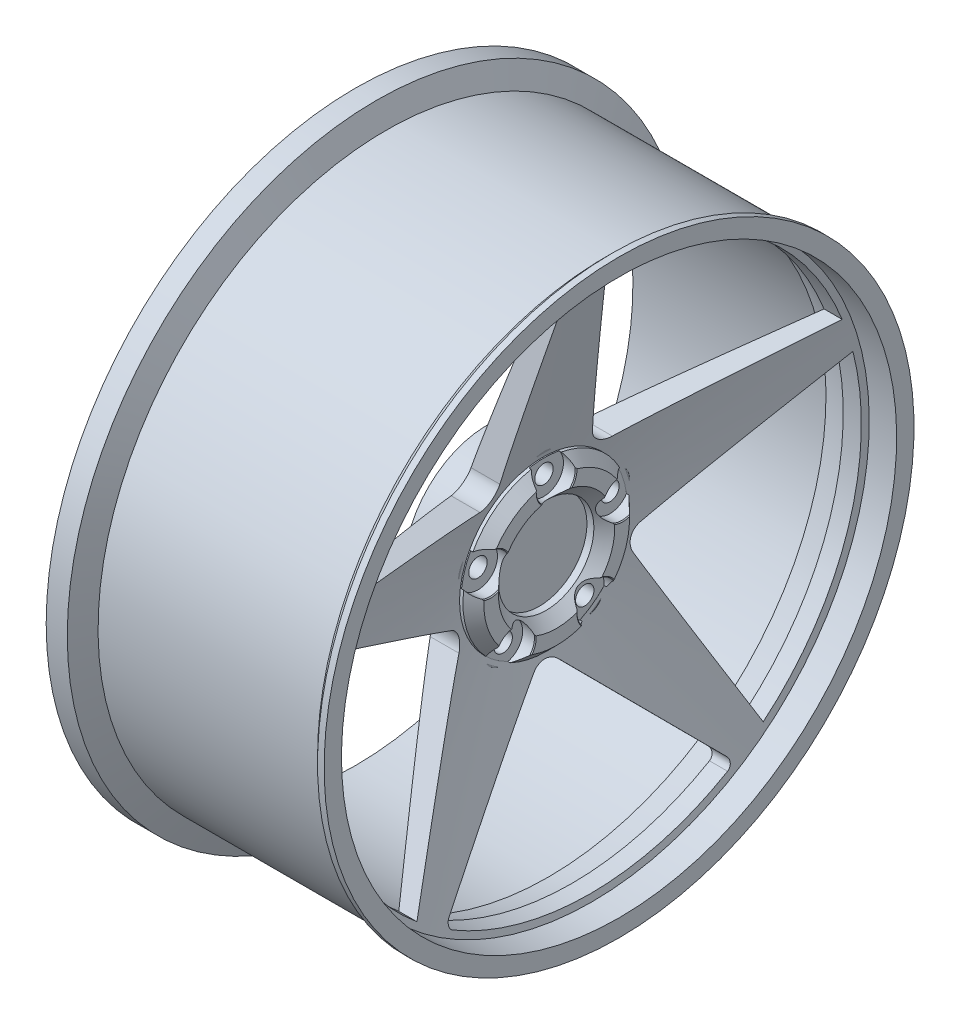
SolidWorks part; units mm, degrees
ref_plane "Front Plane" through (0, 0, 0) normal (0, 0, 1) x (1, 0, 0)
ref_plane "Top Plane" through (0, 0, 0) normal (0, 1, 0) x (1, 0, 0)
ref_plane "Right Plane" through (0, 0, 0) normal (1, 0, 0) x (0, 0, -1)
sketch "Sketch1" plane through (0, 0, 0) normal (0, 0, 1) x (1, 0, 0)
  line L0 (0, 116.7447) -> (25.4, 116.7447)
  line L1 (0, 116.7447) -> (62.0409, -81.8353)
  line L2 (62.0409, -81.8353) -> (44.799, -86.4553)
  line L3 (44.799, -86.4553) -> (-96.52, -86.4553)
  line L4 (-96.52, -86.4553) -> (-96.52, -109.5704)
  line L10 (96.52, -99.1553) -> (96.52, -86.4553)
  line L11 (96.52, -86.4553) -> (76.4676, -86.4553)
  line L12 (76.4676, -86.4553) -> (25.4, 116.7447)
  line L13 (0, 116.7447) -> (0, -86.4553) construction
  line L14 (-96.52, -109.5704) -> (-81.0717, -109.5704)
  line L15 (-81.0717, -109.5704) -> (-74.0404, -94.0753)
  line L16 (-74.0404, -94.0753) -> (86.614, -94.0753)
  line L17 (86.614, -94.0753) -> (91.694, -99.1553)
  line L18 (91.694, -99.1553) -> (96.52, -99.1553)
  point P7 (0, 0)
  point P11 (0, 0)
  point P16 (0, 116.7447)
  point P17 (96.7255, -106.9602)
  point P18 (44.799, -84.864)
  dimension "D1" = 25.4
  dimension "D2" = 15
  dimension "D3" = 96.52
  dimension "D4" = 96.52
  dimension "D5" = 17.35
  dimension "D6" = 7.62
  dimension "D7" = 4.826
  dimension "D8" = 5.08
  dimension "D9" = 12.7
  dimension "D10" = 203.2
  dimension "D11" = 7.62
revolve "Revolve11" add sketch "Sketch1" angle 360 about L0
sketch "Sketch8" plane through (0, 0, 0) normal (1, 0, 0) x (0, 0, -1)
  circle A0 centre (0, 116.7447) radius 60.96
  dimension "D1" = 121.92
extrude "Boss-Extrude1" add sketch "Sketch8" along normal blind 50.8
sketch "Sketch17" plane through (-96.52, 0, 0) normal (-1, 0, 0) x (0, 0, 1)
  line L6 (0, 116.7447) -> (0, -81.8353) construction
  line L7 (0, 55.7847) -> (106.2144, -51.0424)
  line L13 (0, 116.7447) -> (116.7224, -43.9099) construction
  line L14 (0, 116.7447) -> (-116.7224, -43.9099) construction
  line L15 (0, 55.7847) -> (-106.2144, -51.0424)
  circle A5 centre (0, 116.7447) radius 198.58 construction
  circle A6 centre (0, 116.7447) radius 60.96 construction
  arc A7 (-106.2144, -51.0424) -> (106.2144, -51.0424) centre (0, 116.7447) ccw
  dimension "D1" = 36
  dimension "D2" = 72
  dimension "D3" = 12.7
  dimension "D4" = 12.7
extrude "Cut-Extrude29 - Circle" cut sketch "Sketch17" against normal through all
fillet "Fillet6" radius 12.7 1 edges at (29.8828, 55.7847, 0)
fillet "Fillet7" radius 5.08 2 edges at (68.6738, -51.0424, -106.2144) (68.6738, -51.0424, 106.2144)
pattern_circular "CirPattern6" count 5 over 360 about axis through (0, 116.7447, 0) along (1, 0, 0) of "Cut-Extrude29 - Circle", "Fillet6"
hole_wizard "CBORE for 1/2 Hex Head Bolt17" positions "Sketch30" profile "Sketch31" counterbore size "1/2" standard "ANSI Inch" end condition through all
sketch "Sketch30" plane through (50.8, 0, 0) normal (1, 0, 0) x (0, 0, -1)
  line L0 (0, 55.7847) -> (0, 116.7447) construction
  line L2 (0, 116.7447) -> (35.8314, 67.427) construction
  circle A0 centre (0, 116.7447) radius 60.96 construction
  circle A1 centre (0, 116.7447) radius 50.8
  point P13 (29.8595, 75.6466)
  dimension "D1" = 101.6
  dimension "D2" = 36
sketch "Sketch31" plane through (50.8, 75.6466, -29.8595) normal (0, 1, 0) x (0, 0, -1)
  line L0 (0, 0) -> (0, 147.32)
  line L1 (0, 147.32) -> (6.7462, 147.32)
  line L3 (6.7462, 147.32) -> (6.7462, 9.2456)
  line L4 (14.2875, 9.2456) -> (6.7462, 9.2456)
  line L5 (14.2875, 9.2456) -> (14.2875, 0.635)
  line L6 (14.2875, 0.635) -> (14.9225, 0)
  line L7 (14.9225, 0) -> (0, 0)
  line L8 (-14.2875, 0.635) -> (-14.9225, 0) construction
  line L11 (0, -6.35) -> (0, 107.95) construction
  dimension "Thru Hole Dia." = 13.4925
  dimension "Thru Hole Depth" = 147.32
  dimension "C'Bore Dia." = 28.575
  dimension "C'Bore Depth" = 9.2456
  dimension "Near C'Sink Dia." = 29.845
  dimension "Near C'Sink Angle" = 90
pattern_circular "CirPattern10" count 5 over 360 about axis through (0, 116.7447, 0) along (1, 0, 0) of "CBORE for 1/2 Hex Head Bolt17"
sketch "Sketch34" plane through (50.8, 0, 0) normal (1, 0, 0) x (0, 0, -1)
  line L0 (0, 55.7847) -> (0, 116.7447) construction
  circle A0 centre (0, 116.7447) radius 34.925
  dimension "D1" = 69.85
extrude "Cut-Extrude31" cut sketch "Sketch34" against normal blind 12.7
chamfer "Chamfer5" distance 7.62 angle 45 5 edges at (50.8, 55.7847, 0) (50.8, 97.907, 57.9764) (50.8, 97.907, -57.9764) (50.8, 166.0624, -35.8314) (50.8, 166.0624, 35.8314)
chamfer "Chamfer6" distance 7.62 angle 45 1 edges at (50.8, 116.7447, -34.925)
